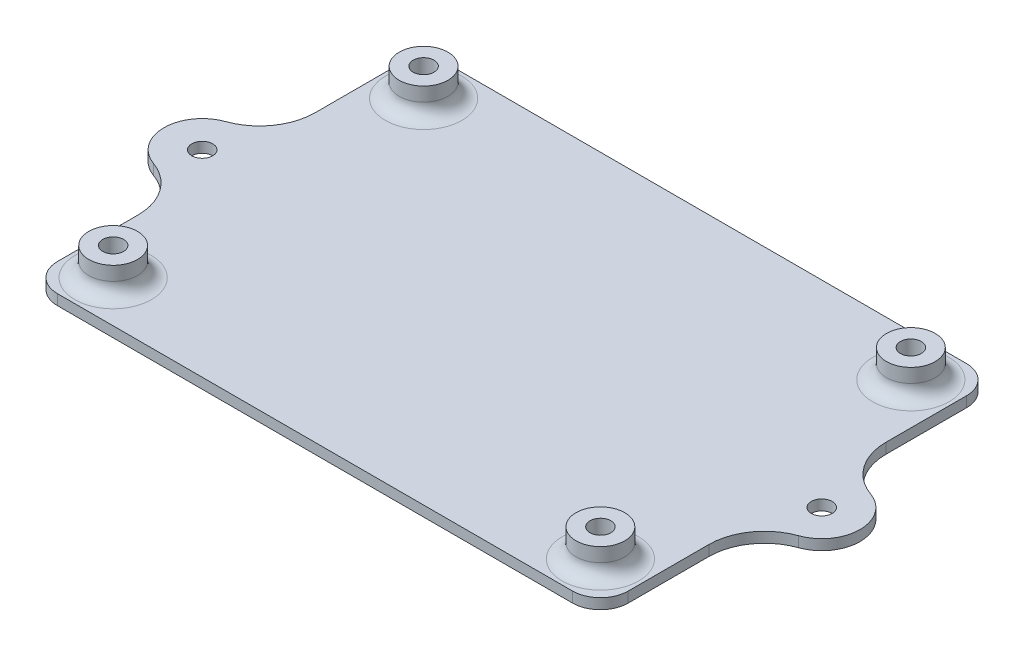
SolidWorks part; units mm, degrees
ref_plane "Front Plane" through (0, 0, 0) normal (0, 0, 1) x (1, 0, 0)
ref_plane "Top Plane" through (0, 0, 0) normal (0, 1, 0) x (1, 0, 0)
ref_plane "Right Plane" through (0, 0, 0) normal (1, 0, 0) x (0, 0, -1)
sketch "Sketch1" plane through (0, 0, 0) normal (0, 1, 0) x (1, 0, 0)
  line L0 (0, 0) -> (-44.5, 0) construction
  line L1 (-41, -28.3) -> (41, -28.3)
  line L2 (-41, -28.3) -> (-41, 28.3)
  line L3 (-41, 28.3) -> (41, 28.3)
  line L4 (41, -28.3) -> (41, 28.3)
  line L5 (-41, -28.3) -> (41, 28.3) construction
  line L6 (-41, 28.3) -> (41, -28.3) construction
  line L7 (-35, -22.3) -> (35, -22.3) construction
  line L8 (-35, -22.3) -> (-35, 22.3) construction
  line L9 (-35, 22.3) -> (35, 22.3) construction
  line L10 (35, -22.3) -> (35, 22.3) construction
  line L11 (-35, -22.3) -> (35, 22.3) construction
  line L12 (-35, 22.3) -> (35, -22.3) construction
  line L13 (0, 0) -> (44.5, 0) construction
  circle A1 centre (-35, 22.3) radius 1.5
  circle A2 centre (35, 22.3) radius 1.5
  circle A3 centre (35, -22.3) radius 1.5
  circle A4 centre (-35, -22.3) radius 1.5
  circle A5 centre (-35, 22.3) radius 3.5
  circle A6 centre (35, 22.3) radius 3.5
  circle A7 centre (35, -22.3) radius 3.5
  circle A8 centre (-35, -22.3) radius 3.5
  circle A9 centre (-44.5, 0) radius 1.5
  circle A10 centre (44.5, 0) radius 1.5
  arc A11 (-41, 12.7279) -> (-46.3333, 5.1854) centre (-49, 12.7279) cw
  arc A12 (-46.3333, 5.1854) -> (-46.3333, -5.1854) centre (-44.5, 0) ccw
  arc A13 (-46.3333, -5.1854) -> (-41, -12.7279) centre (-49, -12.7279) cw
  arc A14 (41, 12.7279) -> (46.3333, 5.1854) centre (49, 12.7279) ccw
  arc A15 (46.3333, 5.1854) -> (46.3333, -5.1854) centre (44.5, 0) cw
  arc A16 (46.3333, -5.1854) -> (41, -12.7279) centre (49, -12.7279) ccw
  circle A17 centre (-35, 22.3) radius 1.5 construction
  point P0 (0, 0)
  point P6 (0, 0)
  point P21 (-38.27, 16.7991)
  point P22 (0, 0)
  point P33 (0, 0)
  point P39 (47.3425, 11.7676)
  point P40 (-38.3636, -19.3173)
  point P43 (40.3746, 28.1532)
  dimension "D1" = 3
  dimension "D3" = 3
  dimension "D6" = 8
  dimension "D2" = 2
  dimension "D4" = 4
  dimension "D5" = 3.5
  dimension "D7" = 6
  dimension "D8" = 6
extrude "Boss-Extrude1" add sketch "Sketch1" along normal blind 1.5 contours L1 L4 L3 L2 A8 A7 A6 A5 | A12 A13 L2 A11 A9 | A16 A15 A14 L4 A10 | A8 A4 | A4 | A7 A3 | A3 | A6 A2 | A2 | A5 A1 | A1 region at (0, 0, 0) region at (-42.2476, 0, 7.9532) region at (41.27, 0, 0) region at (-35, 0, -22.3) region at (35, 0, -22.3) region at (35, 0, 22.3) region at (-35, 0, 22.3) region at (-38.401, 0, -22.3) region at (31.599, 0, -22.3) region at (31.599, 0, 22.3) region at (-38.401, 0, 22.3)
extrude "Boss-Extrude2" add sketch "Sketch1<3>" along normal offset from surface (5.5 mm away) 4 contours A5 A1 | A6 A2 | A7 A3 | A8 A4 region at (-38.401, 0, -22.3) region at (31.599, 0, -22.3) region at (31.599, 0, 22.3) region at (-38.401, 0, 22.3) up to face at (0, 1.5, 0) offset beyond the face yes
sketch "Sketch1<3>" plane through (0, 0, 0) normal (0, 1, 0) x (1, 0, 0) same geometry as "Sketch1"
fillet "Fillet1" radius 2 4 edges at (-35, 1.5, -18.8) (35, 1.5, -18.8) (35, 1.5, 25.8) (-35, 1.5, 25.8)
fillet "Fillet2" radius 4 4 edges at (-41, 0.75, 28.3) (41, 0.75, 28.3) (41, 0.75, -28.3) (-41, 0.75, -28.3)
equation "\"D5@Sketch1\"=2+0.5*\"D3@Sketch1\""
